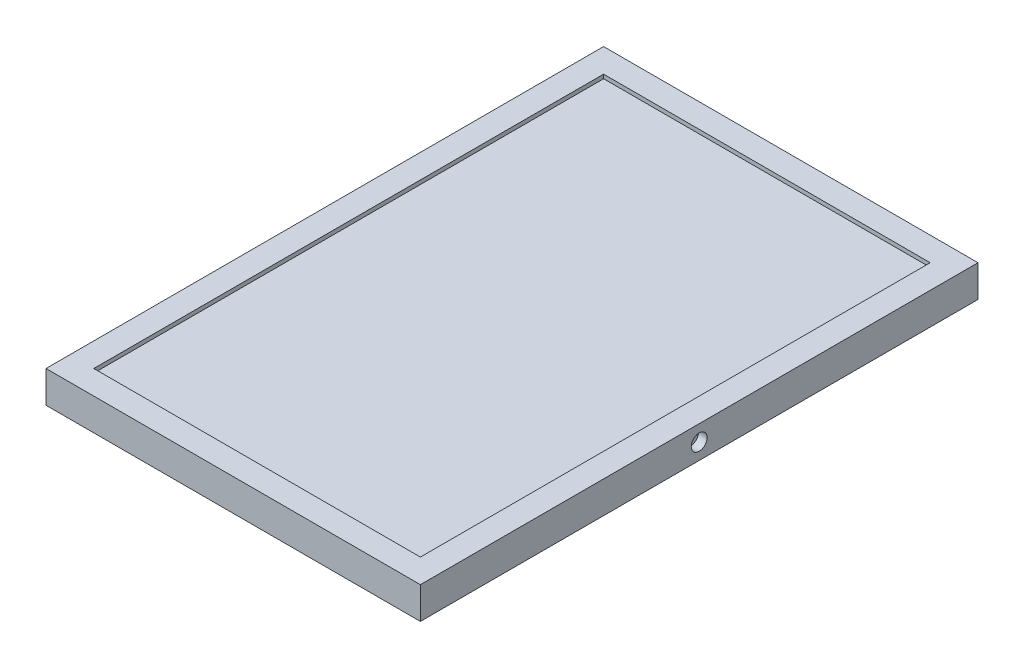
SolidWorks part; units mm, degrees
ref_plane "Front Plane" through (0, 0, 0) normal (0, 0, 1) x (1, 0, 0)
ref_plane "Top Plane" through (0, 0, 0) normal (0, 1, 0) x (1, 0, 0)
ref_plane "Right Plane" through (0, 0, 0) normal (1, 0, 0) x (0, 0, -1)
sketch "Sketch1" plane through (0, 0, 0) normal (0, 1, 0) x (1, 0, 0)
  line L0 (102.5, -160) -> (102.5, 160)
  line L1 (-117.5, -175) -> (117.5, -175)
  line L2 (-117.5, -175) -> (-117.5, 175)
  line L3 (-117.5, 175) -> (117.5, 175)
  line L4 (117.5, -175) -> (117.5, 175)
  line L5 (-117.5, -175) -> (117.5, 175) construction
  line L6 (-117.5, 175) -> (117.5, -175) construction
  line L7 (-102.5, 160) -> (102.5, 160)
  line L8 (-102.5, -160) -> (-102.5, 160)
  line L9 (-102.5, -160) -> (102.5, -160)
  point P0 (0, 0)
  dimension "D1" = 235
  dimension "D2" = 350
  dimension "D3" = 15
extrude "Boss-Extrude1" add sketch "Sketch1" along normal blind 20
extrude "Boss-Extrude2" add sketch "Sketch1<2>" along normal blind 2.5 and the other way blind 2.5 from offset 15 contours L8 L9 L0 L7 region at (0, 0, 0)
sketch "Sketch1<2>" plane through (0, 0, 0) normal (0, 1, 0) x (1, 0, 0) same geometry as "Sketch1"
sketch "Sketch2" plane through (0, 12.5, 0) normal (0, -1, 0) x (1, 0, 0)
  line L0 (0, 0) -> (102.5, 0) construction
  line L1 (102.5, 160) -> (102.5, -160) construction
  line L3 (31.25, -25) -> (71.25, -25)
  line L4 (31.25, -25) -> (31.25, 25)
  line L5 (31.25, 25) -> (71.25, 25)
  line L6 (71.25, -25) -> (71.25, 25)
  line L7 (31.25, -25) -> (71.25, 25) construction
  line L8 (31.25, 25) -> (71.25, -25) construction
  point P6 (51.25, 0)
  dimension "D1" = 40
  dimension "D2" = 50
extrude "Boss-Extrude3" add sketch "Sketch2" along normal blind 12.5
sketch "Sketch3" plane through (-117.5, 0, 0) normal (-1, 0, 0) x (0, 0, 1)
  line L0 (0, 0) -> (0, 20) construction
  line L1 (-175, 20) -> (175, 20) construction
  circle A0 centre (0, 10) radius 5
extrude "Cut-Extrude1" cut sketch "Sketch3" against normal blind 5.5
extrude "Cut-Extrude2" cut sketch "Sketch3<3>" along normal blind 5.5 from surface starting at face at (117.5, 10, 0)
sketch "Sketch3<3>" plane through (-117.5, 0, 0) normal (-1, 0, 0) x (0, 0, 1) same geometry as "Sketch3"
